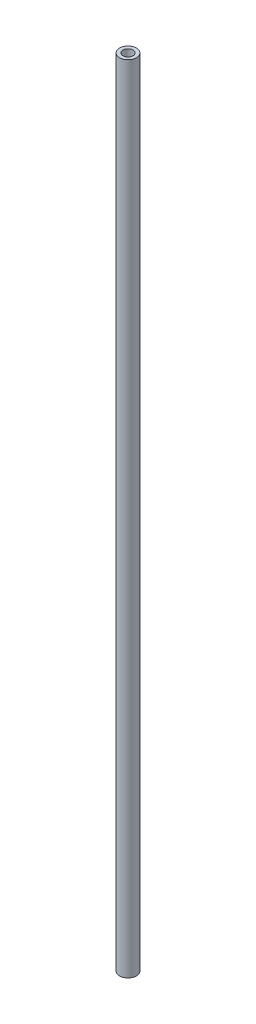
SolidWorks part; units mm, degrees
material "3003-O"
ref_plane "Front Plane" through (0, 0, 0) normal (0, 0, 1) x (1, 0, 0)
ref_plane "Top Plane" through (0, 0, 0) normal (0, 1, 0) x (1, 0, 0)
ref_plane "Right Plane" through (0, 0, 0) normal (1, 0, 0) x (0, 0, -1)
sketch "Sketch1" plane through (0, 0, 0) normal (0, 1, 0) x (1, 0, 0)
  circle A0 centre (0, 0) radius 1.5875
  circle A1 centre (0, 0) radius 0.9525
  dimension "D1" = 3.175
  dimension "D2" = 1.905
extrude "Boss-Extrude1" add sketch "Sketch1" along normal mid plane 150
